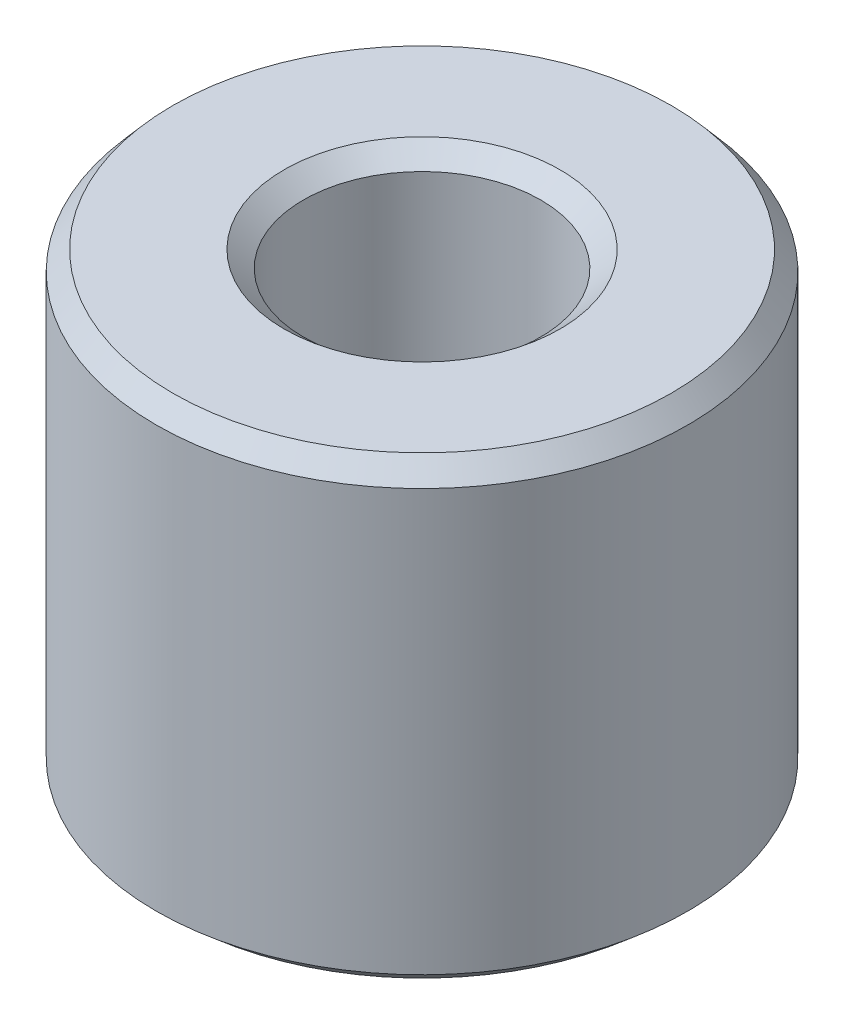
SolidWorks part; units mm, degrees
ref_plane "Front Plane" through (0, 0, 0) normal (0, 0, 1) x (1, 0, 0)
ref_plane "Top Plane" through (0, 0, 0) normal (0, 1, 0) x (1, 0, 0)
ref_plane "Right Plane" through (0, 0, 0) normal (1, 0, 0) x (0, 0, -1)
sketch "Sketch1" plane through (0, 0, 0) normal (0, 1, 0) x (1, 0, 0)
  circle A0 centre (0, 0) radius 45
  dimension "SLEEVE_OD" = 90
extrude "Boss-Extrude1" add sketch "Sketch1" along normal blind 77.3543
sketch "Sketch2" plane through (0, 0, 0) normal (0, 1, 0) x (1, 0, 0)
  circle A0 centre (0, 0) radius 20.1004
  dimension "BORE_D" = 40.2007
extrude "Cut-Extrude1" cut sketch "Sketch2" along normal through all
chamfer "Chamfer1" distance 3.2632 angle 40.629 4 edges at (0, 77.3543, 20.1004) (0, 0, 20.1004) (0, 0, 45) (0, 77.3543, 45) first distance on face at (0, 77.3543, 20.1004) first distance on face at (0, 0, 20.1004) first distance on face at (0, 77.3543, 45)
